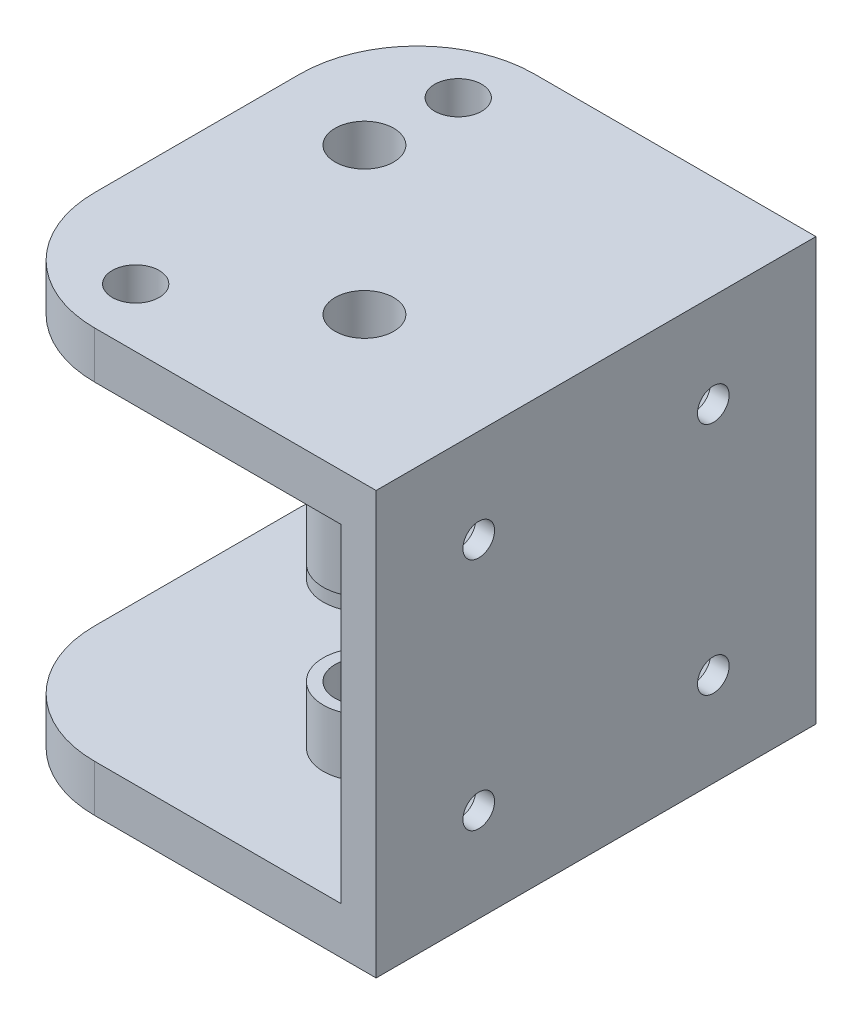
SolidWorks part; units mm, degrees
ref_plane "Front Plane" through (0, 0, 0) normal (0, 0, 1) x (1, 0, 0)
ref_plane "Top Plane" through (0, 0, 0) normal (0, 1, 0) x (1, 0, 0)
ref_plane "Right Plane" through (0, 0, 0) normal (1, 0, 0) x (0, 0, -1)
sketch "TopSketch1" plane through (0, 0, 0) normal (0, 1, 0) x (1, 0, 0)
  line L1 (0, 0) -> (34, 0)
  line L2 (0, 0) -> (0, 37.5)
  line L3 (0, 37.5) -> (34, 37.5)
  line L4 (34, 0) -> (34, 37.5)
  circle A0 centre (8.5, 32.5) radius 2
  circle A1 centre (8.5, 5) radius 2
  circle A2 centre (20.5, 12.5) radius 2.5
  circle A3 centre (8, 25) radius 2.5
  dimension "D7" = 4
  dimension "D8" = 5
  dimension "D2" = 12.5
  dimension "D3" = 12.5
  dimension "D4" = 5
  dimension "D5" = 5
  dimension "D10" = 37.5
  dimension "D9" = 12.5
  dimension "D12" = 13.5
  dimension "D6" = 25.5
  dimension "D11" = 8
  dimension "D13" = 12.5
extrude "Boss-Extrude1" add sketch "TopSketch1" along normal blind 4
sketch "TopLeftRiser" plane through (0, 0, 0) normal (0, -1, 0) x (1, 0, 0)
  line L0 (5.75, -27.681) -> (5.75, -37.5)
  line L1 (34, -37.5) -> (0, -37.5) construction
  line L2 (5.75, -37.5) -> (10.25, -37.5)
  line L3 (10.25, -37.5) -> (10.25, -27.681)
  arc A0 (10.25, -27.681) -> (5.75, -27.681) centre (8, -25) ccw
  circle A1 centre (8, -25) radius 2.5 construction
  circle A2 centre (8, -25) radius 2.5
  point P12 (8, -37.5)
  dimension "D1" = 7
  dimension "D2" = 4.5
extrude "TopLeftRiserBoss-Extrude2" add sketch "TopLeftRiser" along normal blind 4.9
sketch "TopRightRiser" plane through (0, 0, 0) normal (0, -1, 0) x (1, 0, 0)
  line L0 (18.25, -15.181) -> (18.25, -37.5)
  line L1 (34, -37.5) -> (10.25, -37.5) construction
  line L2 (18.25, -37.5) -> (22.75, -37.5)
  line L3 (22.75, -37.5) -> (22.75, -15.181)
  line L4 (5.75, -37.5) -> (10.25, -37.5) construction
  circle A0 centre (20.5, -12.5) radius 2.5
  circle A1 centre (20.5, -12.5) radius 2.5 construction
  arc A2 (22.75, -15.181) -> (18.25, -15.181) centre (20.5, -12.5) ccw
  arc A3 (10.25, -27.681) -> (5.75, -27.681) centre (8, -25) ccw construction
  point P15 (20.5, -37.5)
extrude "topRightRiserBoss-Extrude3" add sketch "TopRightRiser" along normal blind 14.4
sketch "MidWallSketch3" plane through (0, 0, 0) normal (0, -1, 0) x (1, 0, 0)
  line L1 (0, -34.5) -> (10.25, -34.5)
  line L2 (0, -34.5) -> (0, -37.5)
  line L3 (0, -37.5) -> (10.25, -37.5)
  line L4 (10.25, -34.5) -> (10.25, -37.5)
  line L5 (18.25, -34.5) -> (22.75, -34.5)
  line L6 (18.25, -34.5) -> (18.25, -37.5)
  line L7 (18.25, -37.5) -> (22.75, -37.5)
  line L8 (22.75, -34.5) -> (22.75, -37.5)
  line L9 (34, 0) -> (34, -37.5)
  line L10 (34, -37.5) -> (31, -37.5)
  line L11 (31, -37.5) -> (31, 0)
  line L14 (10.25, -37.5) -> (10.25, -27.681) construction
  line L15 (0, -37.5) -> (0, 0) construction
  line L16 (34, -37.5) -> (0, -37.5) construction
  line L17 (31, 0) -> (34, 0)
  line L19 (34, 0) -> (34, -37.5) construction
  line L20 (0, 0) -> (34, 0) construction
  line L21 (22.75, -37.5) -> (22.75, -15.181) construction
  line L22 (18.25, -15.181) -> (18.25, -37.5) construction
  dimension "D1" = 3
extrude "MidWallBoss-Extrude4" add sketch "MidWallSketch3" along normal blind 28
sketch "BottomSketch4" plane through (0, -28, 0) normal (0, -1, 0) x (1, 0, 0)
  line L0 (0, 0) -> (34, 0) construction
  line L1 (0, 0) -> (34, 0)
  line L2 (0, 0) -> (0, -37.5)
  line L3 (0, -37.5) -> (34, -37.5)
  line L4 (34, 0) -> (34, -37.5)
  line L5 (34, 0) -> (34, -37.5) construction
  line L6 (34, -37.5) -> (0, -37.5) construction
extrude "BottomBoss-Extrude5" add sketch "BottomSketch4" along normal blind 4
sketch "GBMountingHolesSketch7" plane through (34, 0, 0) normal (1, 0, 0) x (0, 0, -1)
  line L0 (37.5, 4) -> (37.5, -32) construction
  line L1 (0, 4) -> (37.5, 4) construction
  line L2 (37.5, -32) -> (0, -32) construction
  line L3 (0, 4) -> (0, -32) construction
  circle A0 centre (8.75, -4) radius 1
  circle A1 centre (8.75, -24) radius 1
  circle A2 centre (28.75, -24) radius 1
  circle A3 centre (28.75, -4) radius 1
  dimension "D7" = 2
  dimension "D1" = 20
  dimension "D2" = 8.75
  dimension "D3" = 8
  dimension "D4" = 20
  dimension "D5" = 8
  dimension "D6" = 8.75
extrude "GBMountingHolesCut-Extrude5" cut sketch "GBMountingHolesSketch7" against normal blind 3
sketch "LowerLeftRiser" plane through (0, -28, 0) normal (0, 1, 0) x (1, 0, 0)
  line L0 (5.75, 27.681) -> (5.75, 34.5)
  line L1 (5.75, 34.5) -> (10.25, 34.5)
  line L2 (10.25, 34.5) -> (10.25, 27.681)
  line L3 (5.75, 34.5) -> (10.25, 34.5) construction
  line L4 (5.75, 27.681) -> (5.75, 34.5) construction
  line L5 (10.25, 34.5) -> (10.25, 27.681) construction
  circle A0 centre (8, 25) radius 2.5
  arc A1 (5.75, 27.681) -> (10.25, 27.681) centre (8, 25) ccw
  circle A2 centre (8, 25) radius 2.5 construction
  arc A3 (5.75, 27.681) -> (10.25, 27.681) centre (8, 25) ccw construction
extrude "LowerLeftRiserBoss-Extrude6" add sketch "LowerLeftRiser" along normal blind 14.4
sketch "LowerRightRiser" plane through (0, -28, 0) normal (0, 1, 0) x (1, 0, 0)
  line L0 (18.25, 15.181) -> (18.25, 34.5)
  line L1 (18.25, 34.5) -> (22.75, 34.5)
  line L2 (22.75, 34.5) -> (22.75, 15.181)
  line L3 (18.25, 34.5) -> (22.75, 34.5) construction
  line L4 (18.25, 15.181) -> (18.25, 34.5) construction
  line L5 (22.75, 34.5) -> (22.75, 15.181) construction
  circle A0 centre (20.5, 12.5) radius 2.5
  circle A1 centre (20.5, 12.5) radius 2.5 construction
  arc A2 (18.25, 15.181) -> (22.75, 15.181) centre (20.5, 12.5) ccw
  arc A3 (18.25, 15.181) -> (22.75, 15.181) centre (20.5, 12.5) ccw construction
extrude "LowerRightRiserBoss-Extrude7" add sketch "LowerRightRiser" along normal blind 4.9
fillet "Fillet1" radius 10 3 edges at (0, -30, 0) (0, 2, 0) (0, -14, -37.5)
sketch "TopLeftInset" plane through (0, -4.9, 0) normal (0, -1, 0) x (1, 0, 0)
  line L0 (5.75, -27.681) -> (5.75, -34.5)
  line L1 (5.75, -34.5) -> (10.25, -34.5)
  line L2 (10.25, -34.5) -> (10.25, -27.681)
  line L3 (10.25, -34.5) -> (5.75, -34.5) construction
  line L4 (5.75, -34.5) -> (5.75, -27.681) construction
  line L5 (10.25, -27.681) -> (10.25, -34.5) construction
  arc A0 (5.75, -27.681) -> (10.25, -27.681) centre (8, -25) ccw
  arc A1 (10.25, -27.681) -> (5.75, -27.681) centre (8, -25) ccw construction
extrude "TopLeftInsetCut-Extrude1" cut sketch "TopLeftInset" against normal blind 1
sketch "TopRightInset" plane through (0, -14.4, 0) normal (0, -1, 0) x (1, 0, 0)
  line L0 (18.25, -15.181) -> (18.25, -34.5)
  line L1 (18.25, -34.5) -> (22.75, -34.5)
  line L2 (22.75, -34.5) -> (22.75, -15.181)
  line L3 (22.75, -34.5) -> (18.25, -34.5) construction
  line L4 (18.25, -34.5) -> (18.25, -15.181) construction
  line L5 (22.75, -15.181) -> (22.75, -34.5) construction
  arc A0 (18.25, -15.181) -> (22.75, -15.181) centre (20.5, -12.5) ccw
  arc A1 (22.75, -15.181) -> (18.25, -15.181) centre (20.5, -12.5) ccw construction
extrude "TopRightInsetCut-Extrude2" cut sketch "TopRightInset" against normal blind 1
sketch "LowerLeftInset" plane through (0, -13.6, 0) normal (0, 1, 0) x (1, 0, 0)
  line L0 (5.75, 27.681) -> (5.75, 34.5)
  line L1 (5.75, 34.5) -> (10.25, 34.5)
  line L2 (10.25, 34.5) -> (10.25, 27.681)
  line L3 (5.75, 34.5) -> (10.25, 34.5) construction
  line L4 (5.75, 27.681) -> (5.75, 34.5) construction
  line L5 (10.25, 34.5) -> (10.25, 27.681) construction
  arc A0 (10.25, 27.681) -> (5.75, 27.681) centre (8, 25) ccw
  arc A1 (5.75, 27.681) -> (10.25, 27.681) centre (8, 25) ccw construction
extrude "LowerLeftInsetCut-Extrude3" cut sketch "LowerLeftInset" against normal blind 1
sketch "LowerRightInset" plane through (0, -23.1, 0) normal (0, 1, 0) x (1, 0, 0)
  line L0 (18.25, 15.181) -> (18.25, 34.5)
  line L1 (18.25, 34.5) -> (22.75, 34.5)
  line L2 (22.75, 34.5) -> (22.75, 15.181)
  line L3 (18.25, 34.5) -> (22.75, 34.5) construction
  line L4 (18.25, 15.181) -> (18.25, 34.5) construction
  line L5 (22.75, 34.5) -> (22.75, 15.181) construction
  arc A2 (22.75, 15.181) -> (18.25, 15.181) centre (20.5, 12.5) ccw
  arc A3 (18.25, 15.181) -> (22.75, 15.181) centre (20.5, 12.5) ccw construction
extrude "LowerRightInsetCut-Extrude4" cut sketch "LowerRightInset" against normal blind 1
sketch "PushPinHoleSketch1" plane through (0, -32, 0) normal (0, -1, 0) x (1, 0, 0)
  circle A0 centre (20.5, -12.5) radius 1
  circle A1 centre (8, -25) radius 1
  circle A2 centre (8, -25) radius 2.5 construction
  circle A3 centre (20.5, -12.5) radius 2.5 construction
  dimension "D1" = 2
extrude "PushPinHoleCut-Extrude1" cut sketch "PushPinHoleSketch1" against normal through all
sketch "BottomLeftMountHoleAccessSketch1" plane through (5.75, 0, 0) normal (-1, 0, 0) x (0, 0, 1)
  circle A0 centre (-28.75, -24) radius 1
  dimension "D1" = 2
extrude "BottomLeftMountHoleAccessCut-Extrude2" cut sketch "BottomLeftMountHoleAccessSketch1" against normal blind 15 and the other way blind 10
sketch "TopLeftMountHoleAccessSketch2" plane through (18.25, 0, 0) normal (-1, 0, 0) x (0, 0, 1)
  circle A0 centre (-28.75, -4) radius 1
  circle A1 centre (-28.75, -24) radius 1 construction
extrude "TopLeftMountHoleAccessCut-Extrude3" cut sketch "TopLeftMountHoleAccessSketch2" against normal blind 5 and the other way through all
sketch "Sketch11" plane through (31, 0, 0) normal (-1, 0, 0) x (0, 0, 1)
  point P0 (-8.75, -24)
  point P3 (-28.75, -24)
  point P6 (-8.75, -4)
  point P9 (-28.75, -4)
hole_wizard "CSK for M2.5 Flat Head Machine Screw1" positions "Sketch11" profile "Sketch12" countersink size "M2.5" standard "ANSI Metric" end condition through all
sketch "Sketch12" plane through (31, -24, -8.75) normal (0, 1, 0) x (0, 0, 1)
  line L0 (0, 0) -> (0, 3)
  line L1 (0, 3) -> (1.35, 3)
  line L2 (1.35, 3) -> (1.35, 1.4)
  line L3 (1.35, 1.4) -> (2.75, 0)
  line L5 (2.75, 0) -> (0, 0)
  line L6 (-1.35, 1.4) -> (-2.75, 0) construction
  line L11 (0, -6.35) -> (0, 107.95) construction
  dimension "Thru Hole Dia." = 2.7
  dimension "Thru Hole Depth" = 3
  dimension "Near C'Sink Dia." = 5.5
  dimension "Near C'Sink Angle" = 90
equation "\"GABDepth\"= \"GABDistanceFromBackToFirstPulley\" + \"GABPulleyDDistanceBetween\" + \"GABDistanceFromPulleyToFront\""
equation "\"GABWidth\"= \"StandardWallThickness\" + \"GABDistanceFromLSideToPulley\" + \"GABPulleyWDistanceBetween\" + \"GABDistanceFromPulleyToRSide\""
equation "\"GABLowerHeight\"= 4mm"
equation "\"GABUpperHeight\"= 4mm"
equation "\"GABMidWallHeight\"= 28mm'Must equal 28 or changes alignment"
equation "\"StandardWallThickness\"= 3mm"
equation "\"GABMidShortRiserHeight\"= \"GABMidWallHeight\" / 2 - \"20TGT2PulleyWidth\"'Equals 5.3"
equation "\"LinearGBMountHolesXDistance\"= 20mm'Spec"
equation "\"GABHeight\"= \"GABLowerHeight\" + \"GABMidWallHeight\" + \"GABUpperHeight\""
equation "\"GBMountingHoleDiameter\"= 2mm"
equation "\"GABMidLongRiserHeight\"= \"GABMidWallHeight\" - \"GABMidShortRiserHeight\" - \"20TGT2PulleyWidth\"'Equals 14"
equation "\"GABLRClampHoleOffsetFromSide\"= 5mm"
equation "\"GABDistanceFromBackToFirstPulley\"= 13.5mm"
equation "\"GABPulleyDDistanceBetween\"= 12.5mm'From the100"
equation "\"GABPulleyWDistanceBetween\"= 14.5mm'From the100"
equation "\"GABDistanceFromPulleyToFront\"= 8mm"
equation "\"GABDistanceFromLSideToPulley\"= 9.5mm + \"StandardWallThickness\""
equation "\"GABDistanceFromPulleyToRSide\"= 7.5mm"
equation "\"GABDistanceToFrontClampHoles\"= 8.5mm"
equation "\"SteelShaft5mmHoleDiameter\"= 5mm"
equation "\"20TGT2PulleyWidth\"= 8.7mm'The STL of the Pulley in the diagram is a bit larger"
equation "\"7mmx1mmSpacerDiameter\"= 7mm"
equation "\"7mmx1mmSpacerHeight\"= 1mm"
equation "\"GABRiserBossOffset\"= 0.4mm'Aligns Pulleys inside edges to be 2.5mm (.5mm apart top to bottom)"
equation "\"D2@TopSketch1\" = \"GABPulleyDDistanceBetween\""
equation "\"D3@TopSketch1\" = \"GABPulleyDDistanceBetween\""
equation "\"D4@TopSketch1\" = \"GABLRClampHoleOffsetFromSide\""
equation "\"D5@TopSketch1\" = \"GABLRClampHoleOffsetFromSide\""
equation "\"D8@TopSketch1\" = \"SteelShaft5mmHoleDiameter\""
equation "\"D10@TopSketch1\" = \"GABWidth\""
equation "\"D9@TopSketch1\" = \"GABDistanceFromLSideToPulley\""
equation "\"D12@TopSketch1\"=\"GABDistanceFromBackToFirstPulley\""
equation "\"D1@Boss-Extrude1\"=\"GABUpperHeight\""
equation "\"D1@TopLeftRiser\" = \"7mmx1mmSpacerDiameter\""
equation "\"D1@TopLeftRiserBoss-Extrude2\" = \"GABMidShortRiserHeight\" - \"GABRiserBossOffset\""
equation "\"D1@topRightRiserBoss-Extrude3\" = \"GABMidLongRiserHeight\" + \"GABRiserBossOffset\""
equation "\"D1@MidWallBoss-Extrude4\" = \"GABMidWallHeight\""
equation "\"D1@BottomBoss-Extrude5\" = \"GABLowerHeight\""
equation "\"D1@LowerLeftRiserBoss-Extrude6\" = \"GABMidLongRiserHeight\" + \"GABRiserBossOffset\""
equation "\"D1@LowerRightRiserBoss-Extrude7\" = \"GABMidShortRiserHeight\" - \"GABRiserBossOffset\""
equation "\"D1@GBMountingHolesSketch7\" = \"LinearGBMountHolesXDistance\""
equation "\"D2@GBMountingHolesSketch7\" =  ( \"GABWidth\" - \"LinearGBMountHolesXDistance\" )  / 2"
equation "\"D3@GBMountingHolesSketch7\" =  ( \"GABHeight\" - \"LinearGBMountHolesXDistance\" )  / 2"
equation "\"D4@GBMountingHolesSketch7\"=\"LinearGBMountHolesYDistance\""
equation "\"D7@GBMountingHolesSketch7\"=\"GBMountingHoleDiameter\""
equation "\"D1@TopLeftInsetCut-Extrude1\" = \"7mmx1mmSpacerHeight\""
equation "\"D1@TopRightInsetCut-Extrude2\" = \"7mmx1mmSpacerHeight\""
equation "\"D1@LowerLeftInsetCut-Extrude3\" = \"7mmx1mmSpacerHeight\""
equation "\"D1@LowerRightInsetCut-Extrude4\" = \"7mmx1mmSpacerHeight\""
equation "\"D1@GBMountingHolesCut-Extrude5\" = \"StandardWallThickness\""
equation "\"D6@TopSketch1\"=\"GABDepth\" - \"GABDistanceToFrontClampHoles\""
equation "\"D11@TopSketch1\"=\"GABDistanceFromPulleyToFront\""
equation "\"LinearGBMountHolesYDistance\"= 20mm'Spec"
equation "\"StealPinPushHoleDiameter\"= 2mm"
equation "\"D1@PushPinHoleSketch1\" = \"StealPinPushHoleDiameter\""
equation "\"M3HeatInsertHoleDiameter\"= 4mm'Spec"
equation "\"D7@TopSketch1\"=\"M3HeatInsertHoleDiameter\""
